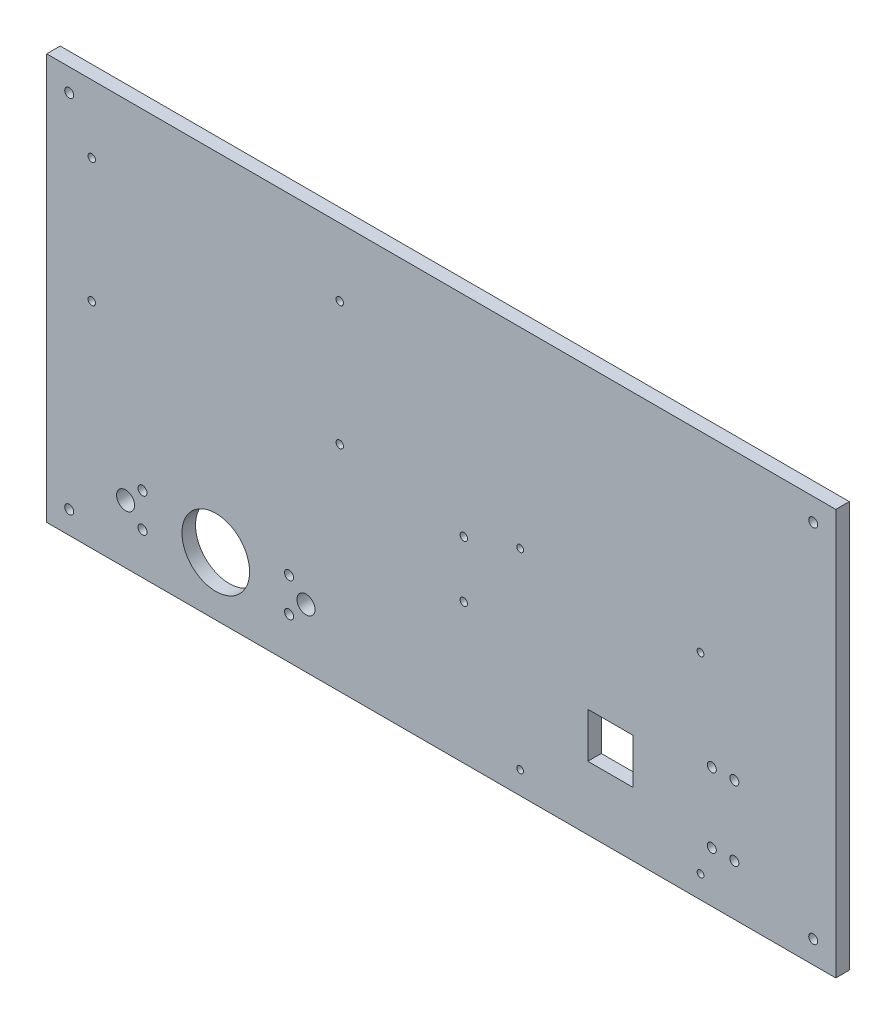
SolidWorks part; units mm, degrees
material "Faia"
ref_plane "Plano frontal" through (0, 0, 0) normal (0, 0, 1) x (1, 0, 0)
ref_plane "Plano superior" through (0, 0, 0) normal (0, 1, 0) x (1, 0, 0)
ref_plane "Plano direito" through (0, 0, 0) normal (1, 0, 0) x (0, 0, -1)
sketch "Esboço1" plane through (0, 0, 0) normal (0, 0, 1) x (1, 0, 0)
  line L0 (175, 0) -> (-175, 0) construction
  line L1 (-175, 90) -> (175, 90)
  line L2 (-175, 90) -> (-175, -90)
  line L3 (-175, -90) -> (175, -90)
  line L4 (175, 90) -> (175, -90)
  line L5 (-175, 90) -> (175, -90) construction
  line L6 (-175, -90) -> (175, 90) construction
  line L7 (95, 0) -> (-255, 0) construction
  line L8 (-108.2276, -64) -> (-89.3617, -64) construction
  line L9 (35, 5) -> (35, -80) construction
  line L10 (115, 5) -> (35, 5) construction
  line L11 (35, -80) -> (115, -80) construction
  line L12 (-100, -58.1086) -> (-100, -85.356) construction
  line L13 (65, -41.75) -> (85, -41.75)
  line L14 (65, -41.75) -> (65, -61.75)
  line L15 (65, -61.75) -> (85, -61.75)
  line L16 (85, -41.75) -> (85, -61.75)
  line L17 (65, -41.75) -> (85, -61.75) construction
  line L18 (65, -61.75) -> (85, -41.75) construction
  line L20 (-45, 5) -> (-155, 5) construction
  line L21 (-45, 5) -> (-45, 60) construction
  line L22 (-45, 60) -> (-155, 60) construction
  line L23 (-155, 5) -> (-155, 60) construction
  line L24 (-45, 5) -> (-155, 60) construction
  line L25 (-45, 60) -> (-155, 5) construction
  circle A0 centre (115, 5) radius 1.5
  circle A1 centre (115, -80) radius 1.5
  circle A2 centre (35, -80) radius 1.5
  circle A3 centre (35, 5) radius 1.5
  circle A4 centre (-132.5, -56.5) radius 2
  circle A5 centre (-67.5, -56.5) radius 2
  circle A6 centre (-100, -64) radius 15
  circle A7 centre (-60, -64) radius 4
  circle A8 centre (-140, -64) radius 4
  circle A9 centre (-67.5, -71.5) radius 2
  circle A10 centre (-132.5, -71.5) radius 2
  circle A11 centre (10, -3) radius 1.65
  circle A12 centre (10, -28) radius 1.65
  circle A13 centre (-155, 60) radius 1.65
  circle A14 centre (-45, 60) radius 1.65
  circle A15 centre (-45, 5) radius 1.65
  circle A16 centre (-155, 5) radius 1.65
  point P0 (0, 0)
  point P21 (5, 0)
  point P23 (75, -51.75)
  point P28 (75, -80)
  point P48 (-100, 32.5)
  point P56 (0, 0)
  point P57 (0, 0)
  dimension "D5" = 3
  dimension "D8" = 32.5
  dimension "D16" = 30
  dimension "D19" = 8
  dimension "D20" = 80
  dimension "D10" = 4
  dimension "D21" = 3.3
  dimension "D26" = 3.3
  dimension "D1" = 350
  dimension "D2" = 180
  dimension "D3" = 60
  dimension "D4" = 85
  dimension "D7" = 80
  dimension "D9" = 15
  dimension "D11" = 25
  dimension "D12" = 10
  dimension "D13" = 20
  dimension "D14" = 20
  dimension "D15" = 28.25
  dimension "D17" = 75
  dimension "D18" = 26
  dimension "D22" = 25
  dimension "D23" = 8
  dimension "D24" = 55
  dimension "D25" = 110
  dimension "D27" = 30
  dimension "D28" = 20
  dimension "D6" = 2
extrude "Ressalto-extrusão1" add sketch "Esboço1" along normal blind 6 contours L4 L1 L2 L3 A3 A1 A0 A2 region at (0.9227, 1.2293, 0)
sketch "Esboço2" plane through (0, 0, 6) normal (0, 0, 1) x (1, 0, 0)
  line L0 (175, 0) -> (-175, 0) construction
  line L1 (-175, 90) -> (175, 90)
  line L2 (-175, 90) -> (-175, -90)
  line L3 (-175, -90) -> (175, -90)
  line L4 (175, 90) -> (175, -90)
  line L5 (-175, 90) -> (175, -90) construction
  line L6 (-175, -90) -> (175, 90) construction
  line L7 (165, 80) -> (165, 90) construction
  line L8 (165, -80) -> (165, -90) construction
  line L9 (-175, 90) -> (175, 90) construction
  circle A0 centre (165, -80) radius 2
  circle A1 centre (165, 80) radius 2
  circle A2 centre (-165, 80) radius 2
  circle A3 centre (-165, -80) radius 2
  point P0 (0, 0)
  point P16 (0.5357, 0)
  dimension "D3" = 4
  dimension "D2" = 180
  dimension "D4" = 10
  dimension "D5" = 10
  dimension "D6" = 10
  dimension "D7" = 10
extrude "Corte-extrusão1" cut sketch "Esboço2" against normal blind 10 contours A2 | A1 | A0 | A3 region at (165, -80, 6) region at (165, 80, 6) region at (-165, 80, 6) region at (-165, -80, 6)
sketch "Esboço3" plane through (0, 0, 6) normal (0, 0, 1) x (1, 0, 0)
  line L0 (175, 90) -> (175, -90) construction
  line L1 (-175, -90) -> (175, -90) construction
  circle A0 centre (130, -67.5) radius 2
  circle A1 centre (130, -36.5) radius 2
  circle A2 centre (120, -36.5) radius 2
  circle A3 centre (120, -67.5) radius 2
  dimension "D2" = 4
  dimension "D1" = 45
  dimension "D3" = 22.5
  dimension "D4" = 31
  dimension "D5" = 10
extrude "Corte-extrusão2" cut sketch "Esboço3" against normal blind 10
